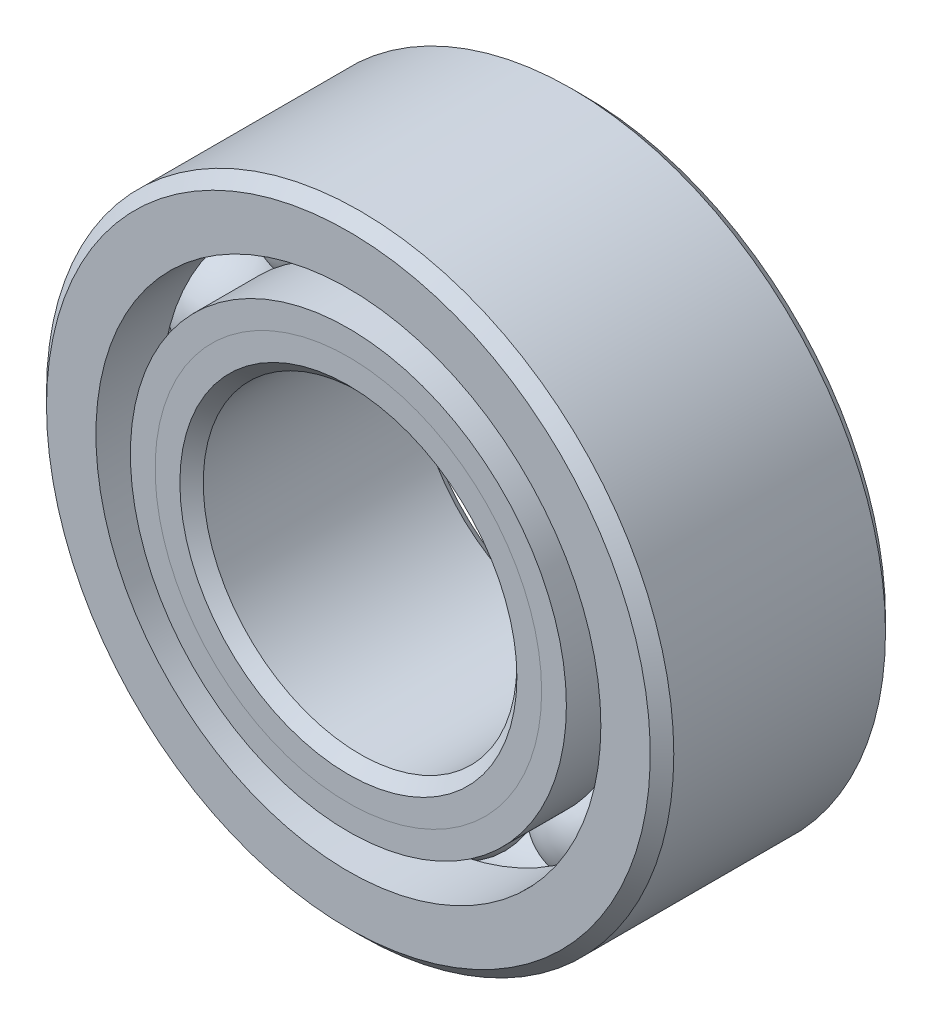
SolidWorks part; units mm, degrees
material "A-Glass Fiber"
ref_plane "Front Plane" through (0, 0, 0) normal (0, 0, 1) x (1, 0, 0)
ref_plane "Top Plane" through (0, 0, 0) normal (0, 1, 0) x (1, 0, 0)
ref_plane "Right Plane" through (0, 0, 0) normal (1, 0, 0) x (0, 0, -1)
sketch "Sketch1" plane through (0, 0, 0) normal (1, 0, 0) x (0, 0, -1)
  line L0 (-1.1906, 0) -> (1.1906, 0) construction
  line L1 (0, 3.175) -> (0, -3.175) construction
  line L2 (1.0716, 3.175) -> (-1.0716, 3.175)
  line L3 (-1.0716, 3.175) -> (-1.1906, 3.0559)
  line L4 (-1.1906, 3.0559) -> (-1.1906, 2.5557)
  line L5 (-1.1906, 2.5557) -> (-0.5292, 2.5557)
  line L6 (1.1906, 2.5557) -> (0.5292, 2.5557)
  line L7 (1.1906, 3.0559) -> (1.1906, 2.5557)
  line L8 (1.0716, 3.175) -> (1.1906, 3.0559)
  line L9 (0, 3.175) -> (0, 2.3812) construction
  line L10 (0, 2.3812) -> (0, 1.5875) construction
  arc A0 (-0.5292, 2.5557) -> (0.5292, 2.5557) centre (0, 2.3812) cw
  point P14 (0, 1.5875)
  dimension "Width" = 2.3813
  dimension "OD" = 6.35
  dimension "D1" = 45
  dimension "D2" = 0.1191
  dimension "D3" = 1.0583
  dimension "D4" = 0.1745
revolve "Revolve1" add sketch "Sketch1" angle 360 about L0
sketch "Sketch2" plane through (0, 0, 0) normal (1, 0, 0) x (0, 0, -1)
  line L0 (-1.1906, 2.2068) -> (-0.5292, 2.2068)
  line L1 (-1.1906, 3.0559) -> (-1.1906, -3.0559) construction
  line L2 (-1.1906, 2.2068) -> (-1.1906, 1.9563)
  line L3 (-1.1906, 1.9563) -> (-0.9401, 1.7058)
  line L4 (-0.9401, 1.7058) -> (0, 1.7058)
  line L5 (0, 3.175) -> (0, -3.175) construction
  line L6 (0, 1.7058) -> (0, 1.8241)
  line L7 (0, 1.8241) -> (0, 1.5875) construction
  line L8 (-1.1906, 2.2068) -> (-1.1906, 1.7058) construction
  line L9 (-1.1906, 1.7058) -> (-0.9401, 1.7058) construction
  arc A0 (-0.5292, 2.2068) -> (0, 1.8241) centre (0, 2.3812) ccw
  arc A1 (0.5292, 2.5557) -> (-0.5292, 2.5557) centre (0, 2.3812) ccw construction
  circle A2 centre (0, 2.3812) radius 0.5572 construction
  dimension "D1" = 45
revolve "Revolve2" add sketch "Sketch2" angle 360 about L0
sketch "Sketch3" plane through (0, 0, 0) normal (1, 0, 0) x (0, 0, -1)
  line L0 (-1.1906, 1.9563) -> (-0.9401, 1.7058)
  line L1 (-0.9401, 1.7058) -> (0, 1.7058)
  line L2 (0, 1.7058) -> (0, 1.8241)
  line L3 (-1.1906, 1.9563) -> (-1.1906, 1.7058)
  line L4 (-1.1906, 2.2068) -> (-1.1906, 1.7058) construction
  line L5 (-1.1906, 1.7058) -> (-1.0723, 1.5875)
  line L6 (-1.0723, 1.5875) -> (1.0716, 1.5875)
  line L7 (1.0716, 3.175) -> (1.0716, -3.175) construction
  line L8 (1.0716, 1.5875) -> (1.1906, 1.7066)
  line L9 (1.1906, -3.0559) -> (1.1906, 3.0559) construction
  line L10 (1.1906, 1.7066) -> (1.1906, 2.2068)
  line L11 (1.1906, 2.2068) -> (0.5292, 2.2068)
  line L13 (1.0716, 3.175) -> (1.1906, 3.0559) construction
  circle A0 centre (0, 2.3812) radius 0.5572 construction
  arc A1 (0.5292, 2.2068) -> (0, 1.8241) centre (0, 2.3812) cw
revolve "Revolve3" add sketch "Sketch3" angle 360 about L0
sketch "Sketch4" plane through (0, 0, 0) normal (1, 0, 0) x (0, 0, -1)
  line L0 (-0.5572, 2.3812) -> (0.5572, 2.3812)
  circle A1 centre (0, 2.3812) radius 0.5572 construction
  arc A2 (-0.5572, 2.3812) -> (0.5572, 2.3812) centre (0, 2.3812) cw
  arc A3 (0.5292, 2.5557) -> (-0.5292, 2.5557) centre (0, 2.3812) ccw construction
revolve "Revolve4" add sketch "Sketch4" angle 360 about L0
ref_axis "Axis1" through (0, 0, -1.1906) along (0, 0, 1)
pattern_circular "CirPattern1" count 10 every 36 about axis through (0, 0, -1.1906) along (0, 0, 1) of bodies 104
equation "\"D2@Sketch1\" = \"Width@Sketch1\"*.05"
equation "\"D3@Sketch1\" = \"Width@Sketch1\"/2.25"
equation "\"D4@Sketch1\" = (((\"OD@Sketch1\"-\"Width@Sketch1\")/2)/3.25)/3.5"
equation "\"D2@CirPattern1\" = 360/\"Balls@CirPattern1\""
